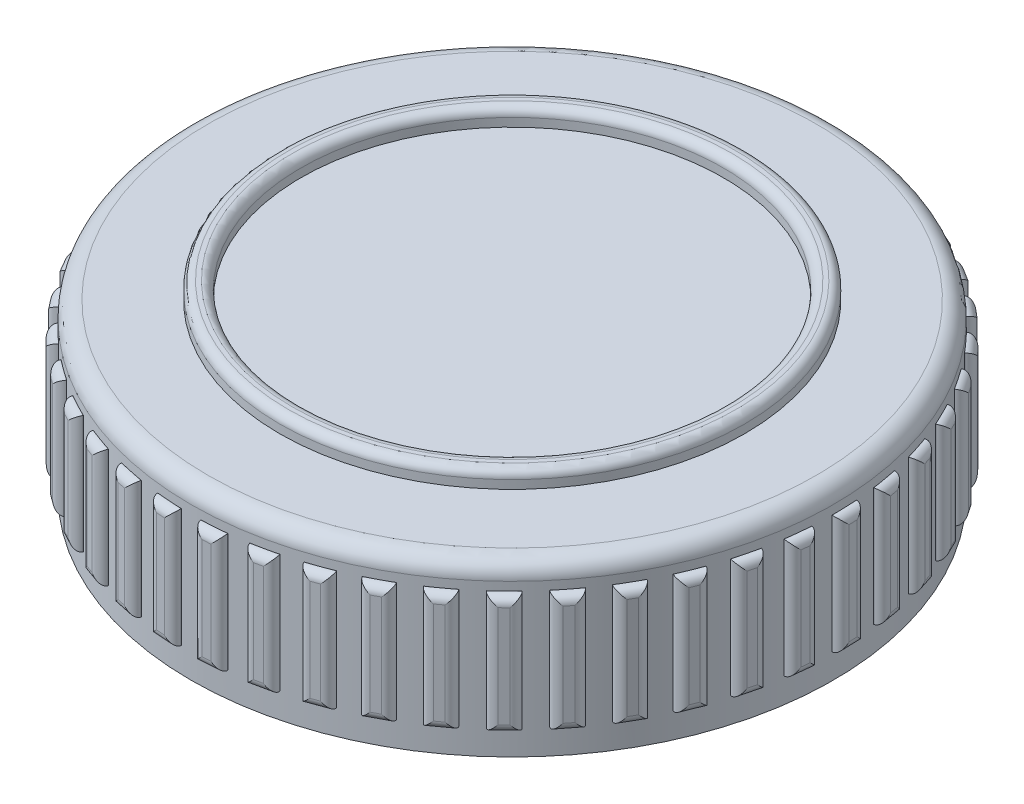
SolidWorks part; units mm, degrees
ref_plane "Front Plane" through (0, 0, 0) normal (0, 0, 1) x (1, 0, 0)
ref_plane "Top Plane" through (0, 0, 0) normal (0, 1, 0) x (1, 0, 0)
ref_plane "Right Plane" through (0, 0, 0) normal (1, 0, 0) x (0, 0, -1)
sketch "Sketch1" plane through (0, 0, 0) normal (0, 1, 0) x (1, 0, 0)
  circle A0 centre (0, 0) radius 38
  dimension "D1" = 76
extrude "Boss-Extrude1" add sketch "Sketch1" along normal blind 20
shell "Shell1" thickness 3 removed face at (0, 0, 38)
sketch "Sketch2" plane through (0, 0, 0) normal (0, 1, 0) x (1, 0, 0)
  circle A0 centre (0, 0) radius 27.5
  circle A1 centre (0, 0) radius 25
  dimension "D1" = 55
  dimension "D2" = 50
extrude "Boss-Extrude2" add sketch "Sketch2" along normal blind 2 from surface starting at face at (0, 20, 38)
sketch "Sketch4" plane through (0, 0, 0) normal (0, 1, 0) x (1, 0, 0)
  line L0 (-1.5, 37.9147) -> (-1.5, 39)
  line L1 (-1.5, -39) -> (1.5, -39) construction
  line L2 (-1.5, -39) -> (-1.5, 39) construction
  line L3 (-1.5, 39) -> (1.5, 39) construction
  line L4 (1.5, -39) -> (1.5, 39) construction
  line L5 (-1.5, -39) -> (1.5, 39) construction
  line L6 (-1.5, 39) -> (1.5, -39) construction
  line L7 (-1.5, 39) -> (1.5, 39)
  line L8 (1.5, 39) -> (1.5, 37.9147)
  line L9 (1.5, 37.9147) -> (-1.5, 37.9147)
  point P0 (0, 0)
  point P10 (0, 0)
  point P11 (0, 0)
  dimension "D1" = 3
  dimension "D2" = 78
  dimension "D3" = 1.0853
extrude "Boss-Extrude3" add sketch "Sketch4" along normal blind 14 from offset 3
fillet "Fillet1" radius 1 4 edges at (1.5, 10, -39) (0, 17, -39) (-1.5, 10, -39) (0, 3, -39)
pattern_circular "CirPattern2" count 45 over 360 about axis through (0, 20, 0) along (0, 1, 0) of "Fillet1", "Boss-Extrude3"
fillet "Fillet2" radius 1 2 edges at (0, 22, 25) (0, 22, 27.5)
fillet "Fillet3" radius 2 1 edges at (0, 20, 38)
